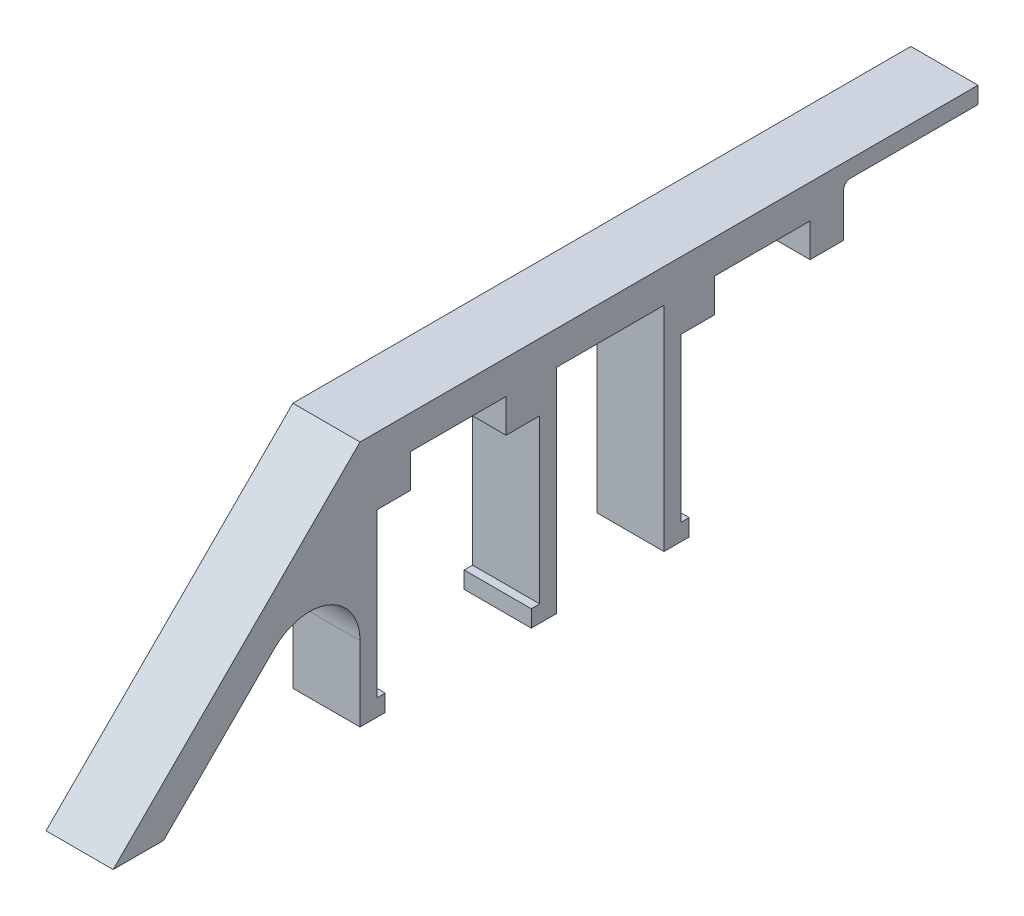
SolidWorks part; units mm, degrees
ref_plane "Front" through (0, 0, 0) normal (0, 0, 1) x (1, 0, 0)
ref_plane "Top" through (0, 0, 0) normal (0, 1, 0) x (1, 0, 0)
ref_plane "Right" through (0, 0, 0) normal (1, 0, 0) x (0, 0, -1)
sketch "Sketch1" plane through (0, 0, 0) normal (1, 0, 0) x (0, 0, -1)
  line L16 (-5, 68.5) -> (-5, -5)
  line L17 (-5, -5) -> (2.5, -5)
  line L18 (2.5, -5) -> (2.5, 0)
  line L19 (2.5, 0) -> (0, 0)
  line L20 (0, 0) -> (0, 48.5)
  line L21 (0, 48.5) -> (10, 48.5)
  line L22 (10, 48.5) -> (10, 58.5)
  line L23 (10, 58.5) -> (38.5, 58.5)
  line L24 (38.5, 58.5) -> (38.5, 48.5)
  line L25 (38.5, 48.5) -> (48.5, 48.5)
  line L26 (48.5, 48.5) -> (48.5, 0)
  line L27 (48.5, 0) -> (53.5, 0)
  line L28 (53.5, 0) -> (53.5, 58.5)
  line L29 (53.5, 58.5) -> (85.5, 58.5)
  line L30 (69.5, 58.5) -> (69.5, 90.1855)
  line L31 (-5, 68.5) -> (144, 68.5)
  line L32 (85.5, 0) -> (85.5, 58.5)
  line L33 (90.5, 0) -> (85.5, 0)
  line L34 (90.5, 48.5) -> (90.5, 0)
  line L35 (100.5, 48.5) -> (90.5, 48.5)
  line L36 (100.5, 58.5) -> (100.5, 48.5)
  line L37 (129, 58.5) -> (100.5, 58.5)
  line L38 (129, 48.5) -> (129, 58.5)
  line L39 (139, 48.5) -> (129, 48.5)
  line L40 (139, 0) -> (139, 48.5)
  line L41 (136.5, 0) -> (139, 0)
  line L42 (136.5, -5) -> (136.5, 0)
  line L43 (144, -5) -> (136.5, -5)
  line L44 (144, 68.5) -> (144, -5)
  line L45 (48.5, 0) -> (46, 0)
  line L46 (46, 0) -> (46, -5)
  line L47 (53.5, 0) -> (53.5, -5)
  line L48 (53.5, -5) -> (46, -5)
  line L49 (85.5, 0) -> (85.5, -5)
  line L50 (85.5, -5) -> (93, -5)
  line L51 (93, 0) -> (93, -5)
  line L52 (90.5, 0) -> (93, 0)
  line L53 (90.5, 0) -> (85.5, 0)
  line L54 (139, 48.5) -> (139, 68.5)
  line L55 (-5, 68.5) -> (-78.5, -5)
  line L56 (-5, -5) -> (-78.5, -5)
  line L57 (-78.5, -5) -> (-63.5, -5)
  line L58 (-63.5, -5) -> (-5, 53.5)
  line L59 (139, 63.5) -> (179, 63.5)
  line L60 (179, 63.5) -> (179, 68.5)
  line L61 (179, 68.5) -> (144, 68.5)
  point P9 (51, 0)
  point P32 (69.5, 68.5)
  dimension "D1" = 20
  dimension "D2" = 20
  dimension "D3" = 2.5
  dimension "D4" = 5
  dimension "D5" = 48.5
  dimension "D6" = 42
  dimension "D7" = 10
  dimension "D8" = 10
  dimension "D9" = 5
  dimension "D10" = 48.5
  dimension "D11" = 48.5
  dimension "D12" = 5
  dimension "D13" = 5
  dimension "D14" = 2.5
  dimension "D15" = 45
  dimension "D16" = 90
  dimension "D17" = 15
  dimension "D18" = 10
  dimension "D19" = 0
  dimension "D20" = 15
  dimension "D21" = 35
  dimension "D22" = 5
extrude "Boss-Extrude2" add sketch "Sketch1" along normal blind 20 contours L56 L58 L16 L55 | L31 L16 L17 L18 L19 L20 L21 L22 L23 L24 L25 L26 L27 L28 L29 L30 | L39 L54 L31 L30 L29 L32 L33 L34 L35 L36 L37 L38 | L52 L33 L49 L50 L51 | L48 L47 L27 L45 L46 | L44 L31 L54 | L60 L61 L44 region at (0, 67.4535, -32.25) region at (0, 28.142, 38.142) region at (0, 67.5242, -104.25) region at (0, 66, -141.5) region at (0, 66, -161.5) region at (0, -2.5, -49.75) region at (0, -2.5, -89.25)
fillet "Fillet1" radius 15 1 edges at (10, 53.5, 5)
fillet "Fillet2" radius 2 1 edges at (10, 63.5, -139)
